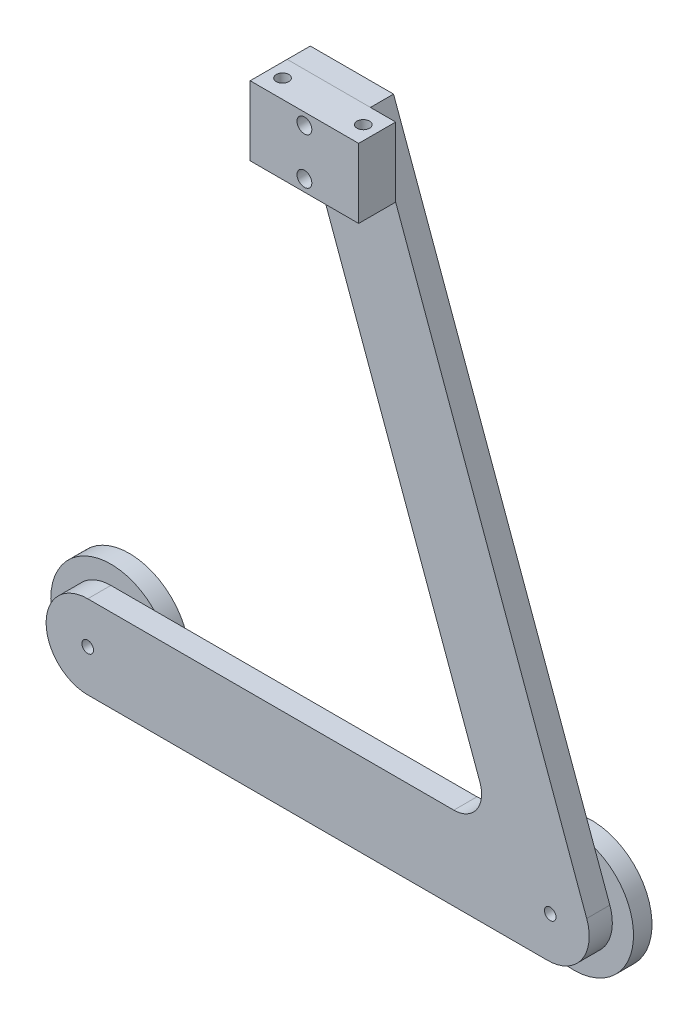
SolidWorks part; units mm, degrees
ref_plane "正面" through (0, 0, 0) normal (0, 0, 1) x (1, 0, 0)
ref_plane "平面" through (0, 0, 0) normal (0, 1, 0) x (1, 0, 0)
ref_plane "右側面" through (0, 0, 0) normal (1, 0, 0) x (0, 0, -1)
sketch "ｽｹｯﾁ1" plane through (0, 0, 0) normal (0, 0, 1) x (1, 0, 0)
  line L0 (-44.6071, 122.557) -> (-2.9307, 8.0521)
  line L1 (-8.5689, 0) -> (-87.7243, 0)
  line L3 (-87.7243, -18) -> (11.6981, -18)
  line L4 (20.1554, -5.9218) -> (-26.6071, 122.557)
  line L5 (-26.6071, 122.557) -> (-44.6071, 122.557)
  line L6 (-87.7243, -9) -> (12.2757, -9) construction
  line L7 (12.2757, -9) -> (-35.6071, 122.557) construction
  arc A0 (11.6981, -18) -> (20.1554, -5.9218) centre (11.6981, -9) ccw
  arc A1 (-96.7243, -9) -> (-87.7243, -18) centre (-87.7243, -9) ccw
  arc A2 (-87.7243, 0) -> (-96.7243, -9) centre (-87.7243, -9) ccw
  circle A3 centre (12.2757, -9) radius 1.25
  circle A4 centre (-87.7243, -9) radius 1.25
  arc A5 (-2.9307, 8.0521) -> (-8.5689, 0) centre (-8.5689, 6) cw
  point P14 (-87.7243, -18)
  point P17 (-87.7243, 0)
  point P20 (0, 0)
  point P21 (-15.1547, 109.8746)
  dimension "D1" = 6
  dimension "D6" = 2.5
  dimension "D2" = 140
  dimension "D3" = 100
  dimension "D4" = 18
  dimension "D5" = 18
  dimension "D7" = 70
extrude "ﾎﾞｽ - 押し出し1" add sketch "ｽｹｯﾁ1" along normal blind 5
sketch "ｽｹｯﾁ2" plane through (0, 0, 5) normal (0, 0, 1) x (1, 0, 0)
  line L0 (20.1554, -5.9218) -> (-26.6071, 122.557) construction
  line L1 (-44.6071, 122.557) -> (-21.1475, 122.557)
  line L2 (-44.6071, 122.557) -> (-44.6071, 107.557)
  line L3 (-44.6071, 107.557) -> (-21.1475, 107.557)
  line L4 (-21.1475, 122.557) -> (-21.1475, 107.557)
  line L5 (-44.6071, 115.057) -> (-21.1475, 115.057) construction
  line L7 (-32.8773, 122.557) -> (-32.8773, 107.557) construction
  dimension "D1" = 15
extrude "ﾎﾞｽ - 押し出し2" add sketch "ｽｹｯﾁ2" along normal blind 8 separate body
sketch "ｽｹｯﾁ3" plane through (0, 0, 13) normal (0, 0, 1) x (1, 0, 0)
  line L0 (-44.6071, 115.057) -> (-21.1475, 115.057) construction
  line L1 (-44.6071, 122.557) -> (-44.6071, 107.557) construction
  line L2 (-21.1475, 107.557) -> (-21.1475, 122.557) construction
  line L4 (-21.1475, 122.557) -> (-44.6071, 122.557) construction
  line L5 (-32.8773, 122.557) -> (-32.8773, 115.057) construction
  circle A0 centre (-32.8773, 120.057) radius 1.6
  circle A1 centre (-32.8773, 110.057) radius 1.6
  dimension "D1" = 3.2
  dimension "D2" = 10
extrude "ｶｯﾄ - 押し出し1" cut sketch "ｽｹｯﾁ3" against normal through all
sketch "ｽｹｯﾁ4" plane through (0, 107.557, 0) normal (0, -1, 0) x (1, 0, 0)
  line L0 (-21.1475, 9) -> (-44.6071, 9) construction
  line L1 (-21.1475, 13) -> (-21.1475, 5) construction
  line L2 (-44.6071, 13) -> (-44.6071, 5) construction
  line L4 (-44.6071, 13) -> (-21.1475, 13) construction
  line L5 (-32.8773, 13) -> (-32.8773, 5) construction
  line L6 (-44.6071, 5) -> (-21.1475, 5) construction
  circle A0 centre (-24.1475, 9) radius 1.35
  circle A1 centre (-41.6071, 9) radius 1.35
  dimension "D1" = 2.7
  dimension "D2" = 3
extrude "ｶｯﾄ - 押し出し2" cut sketch "ｽｹｯﾁ4" against normal through all
sketch "ｽｹｯﾁ6" plane through (0, 0, 0) normal (0, 0, -1) x (-1, 0, 0)
  circle A0 centre (-12.2757, -9) radius 3
  circle A1 centre (87.7243, -9) radius 3
  circle A2 centre (87.7243, -9) radius 1.25 construction
  circle A3 centre (-12.2757, -9) radius 1.25 construction
  circle A4 centre (87.7243, -9) radius 1.25
  circle A5 centre (-12.2757, -9) radius 1.25
  dimension "D1" = 6
extrude "ﾎﾞｽ - 押し出し3" add sketch "ｽｹｯﾁ6" along normal blind 5 separate body
sketch "ｽｹｯﾁ7" plane through (0, 0, 0) normal (0, 0, -1) x (-1, 0, 0)
  circle A0 centre (87.7243, -9) radius 3 construction
  circle A1 centre (-12.2757, -9) radius 3 construction
  circle A2 centre (87.7243, -9) radius 3
  circle A3 centre (-12.2757, -9) radius 3
  circle A4 centre (-12.2757, -9) radius 13
  circle A5 centre (87.7243, -9) radius 13
  dimension "D1" = 26
extrude "ﾎﾞｽ - 押し出し4" add sketch "ｽｹｯﾁ7" along normal blind 4 separate body
